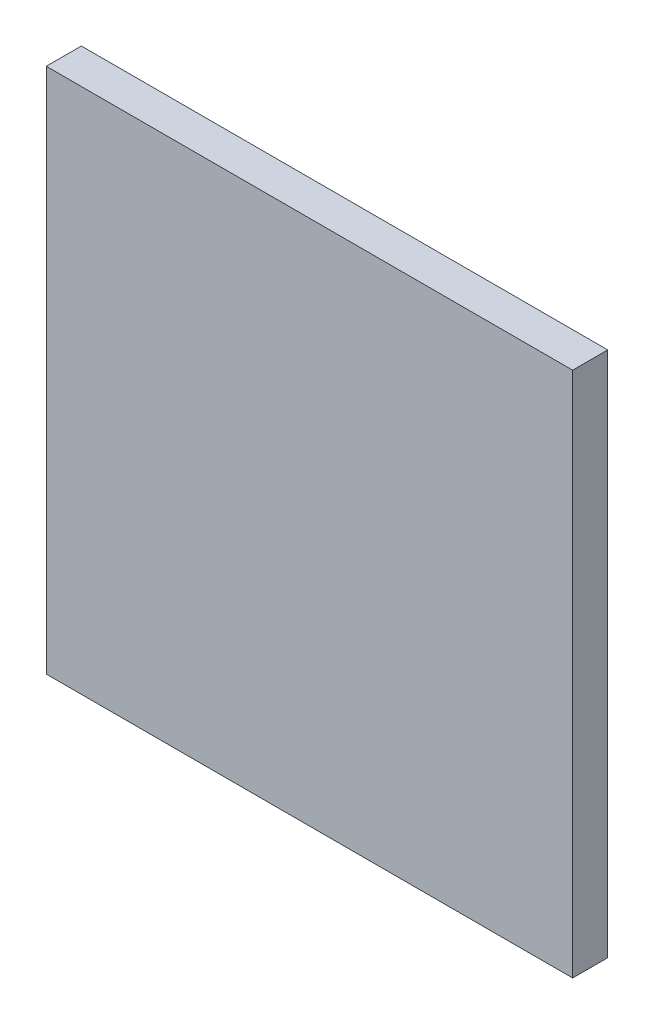
SolidWorks part; units mm, degrees
ref_plane "Ön Düzlem" through (0, 0, 0) normal (0, 0, 1) x (1, 0, 0)
ref_plane "Üst Düzlem" through (0, 0, 0) normal (0, 1, 0) x (1, 0, 0)
ref_plane "Sağ Düzlem" through (0, 0, 0) normal (1, 0, 0) x (0, 0, -1)
sketch "Çizim1" plane through (0, 0, 0) normal (0, 0, 1) x (1, 0, 0)
  line L1 (0, 0) -> (300, 0)
  line L2 (0, 0) -> (0, -300)
  line L3 (0, -300) -> (300, -300)
  line L4 (300, 0) -> (300, -300)
  dimension "D1" = 300
  dimension "D2" = 300
base flange "Taban-Flanş1" sketch "Çizim1" thickness 20 reverse thickness direction no parameters "D1"=2.5
sketch "Büküm-Çizgileri1" [suppressed] plane through (0, 0, 0) normal (0, 1, 0) x (1, 0, 0)
sketch "Sınırlandırma-Kutusu1" [suppressed] plane through (0, 0, 0) normal (0, 1, 0) x (1, 0, 0)
sheet metal parameters "Sac-Levha1" thickness 20 parameters "D1"=2.5
flat pattern "Düz-Çoğaltma1" [suppressed]
sketch "Büküm-Çizgileri2" plane through (0, 0, 0) normal (0, 1, 0) x (1, 0, 0)
sketch3d "Sınırlandırma-Kutusu2" [suppressed]
  line L0 (0, -300, 0) -> (300, -300, 0) construction
  line L1 (0, 0, 0) -> (300, 0, 0) construction
  line L2 (0, -300, 0) -> (0, 0, 0) construction
  line L3 (300, -300, 0) -> (300, 0, 0) construction
